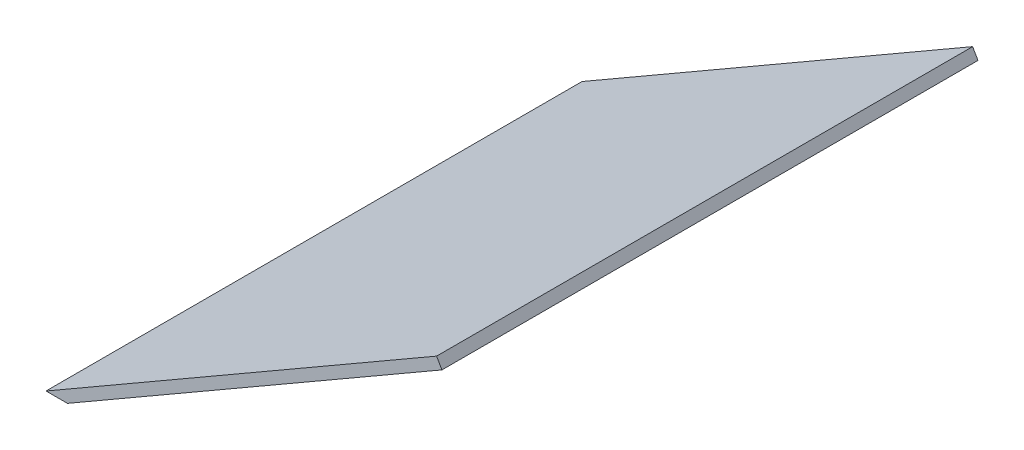
SolidWorks part; units mm, degrees
ref_plane "Front Plane" through (0, 0, 0) normal (0, 0, 1) x (1, 0, 0)
ref_plane "Top Plane" through (0, 0, 0) normal (0, 1, 0) x (1, 0, 0)
ref_plane "Right Plane" through (0, 0, 0) normal (1, 0, 0) x (0, 0, -1)
sketch "Sketch1" plane through (0, 0, 0) normal (0, 0, 1) x (1, 0, 0)
  line L0 (0, 0) -> (6, 0)
  line L1 (6, 0) -> (110.7977, 60.505)
  line L2 (6, 0) -> (50006, 0) construction
  line L3 (110.7977, 60.505) -> (109.2977, 63.1031)
  line L4 (0, 0) -> (109.2977, 63.1031)
  dimension "D1" = 6
  dimension "D2" = 121.01
  dimension "D3" = 30
  dimension "D4" = 3
extrude "Boss-Extrude1" add sketch "Sketch1" along normal blind 150
